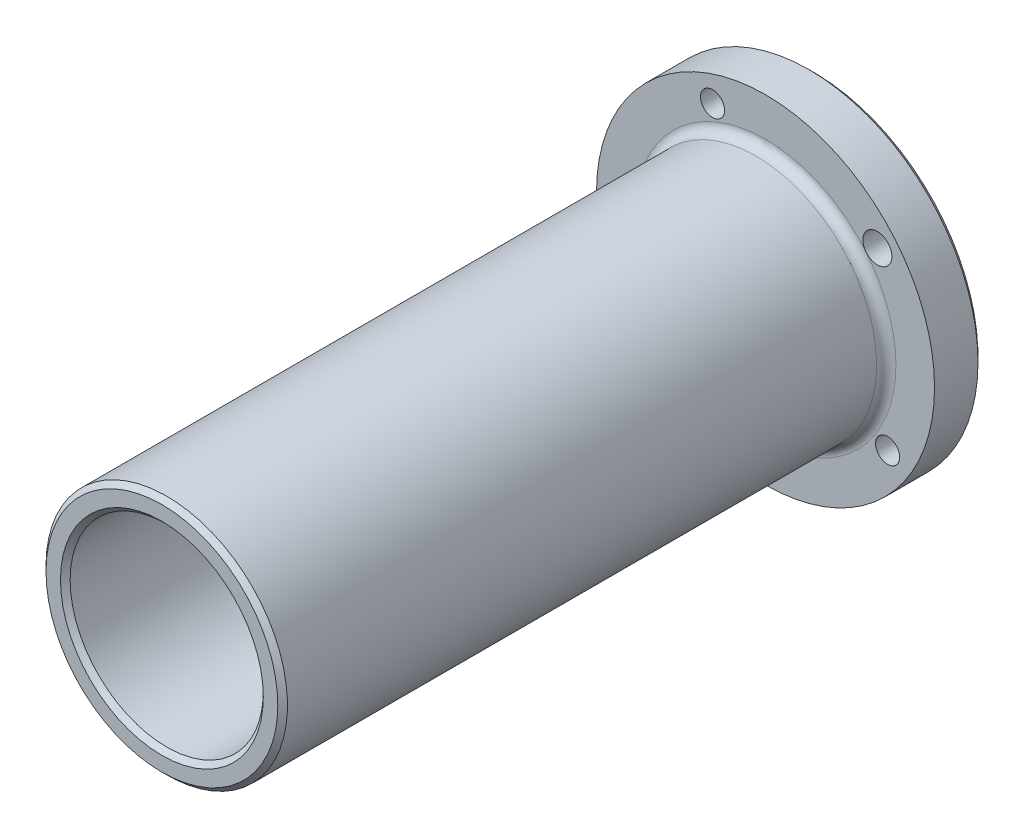
SolidWorks part; units mm, degrees
material "Q235"
ref_plane "前视基准面" through (0, 0, 0) normal (0, 0, 1) x (1, 0, 0)
ref_plane "上视基准面" through (0, 0, 0) normal (0, 1, 0) x (1, 0, 0)
ref_plane "右视基准面" through (0, 0, 0) normal (1, 0, 0) x (0, 0, -1)
sketch "草图1" plane through (0, 0, 0) normal (0, 0, 1) x (1, 0, 0)
  circle A0 centre (70, 0) radius 35
  dimension "D1" = 70
extrude "凸台-拉伸1" add sketch "草图1" along normal blind 5
sketch "草图2" plane through (0, 0, 0) normal (0, 0, -1) x (-1, 0, 0)
  circle A0 centre (-70, 0) radius 25
  dimension "D1" = 50
extrude "凸台-拉伸2" add sketch "草图2" along normal blind 135
sketch "草图4" plane through (0, 0, 0) normal (0, 0, -1) x (-1, 0, 0)
  circle A1 centre (-70, 0) radius 35
  circle A2 centre (-70, 0) radius 35 construction
extrude "切除-拉伸2" cut sketch "草图4" against normal blind 5
sketch "草图9" plane through (0, 0, -135) normal (0, 0, -1) x (-1, 0, 0)
  circle A0 centre (-70, 0) radius 35
  dimension "D1" = 70
extrude "凸台-拉伸3" add sketch "草图9" against normal blind 10
chamfer "倒角1" distance 1 angle 45 2 edges at (45, 0, 0) (35, 0, -135)
hole_wizard "M6 螺纹孔1" positions "草图6" profile "草图5" tap size "M6" standard "GB"
sketch "草图6" plane through (0, 0, -135) normal (0, 0, -1) x (-1, 0, 0)
  point P1 (-62.4582, -29.0365)
  point P4 (-95.2849, -16.1455)
  point P7 (-59.0342, 27.924)
  point P10 (-40.0541, -1.8001)
sketch "草图5" plane through (62.4582, -29.0365, -135) normal (1, 0, 0) x (0, 1, 0)
  line L0 (0, 0) -> (0, 26.5022)
  line L1 (0, 26.5022) -> (2.5, 25)
  line L2 (2.5, 25) -> (2.5, 0)
  line L5 (2.5, 0) -> (0, 0)
  line L10 (0, 26.5022) -> (-2.5, 25) construction
  line L11 (0, -6.35) -> (0, 107.95) construction
  dimension "螺纹孔钻头直径" = 5
  dimension "螺纹孔钻头深度" = 25
  dimension "导头角度" = 118
cosmetic thread "孔螺蚊线1" parameters "D1"=12, "D2"=6
cosmetic thread "孔螺蚊线2" parameters "D1"=12, "D2"=6
cosmetic thread "孔螺蚊线3" parameters "D1"=12, "D2"=6
cosmetic thread "孔螺蚊线4" parameters "D1"=12, "D2"=6
hole_wizard "Ø6.0 (6) 直径孔1" positions "草图8" profile "草图7" hole size "Ø6.0" standard "ISO"
sketch "草图8" plane through (0, 0, -135) normal (0, 0, -1) x (-1, 0, 0)
  point P1 (-93.1687, 19.0581)
sketch "草图7" plane through (93.1687, 19.0581, -135) normal (1, 0, 0) x (0, 1, 0)
  line L0 (0, 0) -> (0, 21.8026)
  line L1 (0, 21.8026) -> (3, 20)
  line L2 (3, 20) -> (3, 0)
  line L5 (3, 0) -> (0, 0)
  line L10 (0, 21.8026) -> (-3, 20) construction
  line L11 (0, -6.35) -> (0, 107.95) construction
  dimension "孔直径" = 6
  dimension "孔深度" = 20
  dimension "导头角度" = 118
chamfer "倒角2" distance 0.5 angle 45 1 edges at (90.1687, 19.0581, -135)
sketch "草图10" plane through (0, 0, -135) normal (0, 0, -1) x (-1, 0, 0)
  circle A0 centre (-70, 0) radius 20
  dimension "D1" = 40
extrude "切除-拉伸3" cut sketch "草图10" against normal through all
fillet "圆角1" radius 2 1 edges at (45, 0, -125)
chamfer "倒角3" distance 1 angle 45 2 edges at (50, 0, 0) (50, 0, -135)
